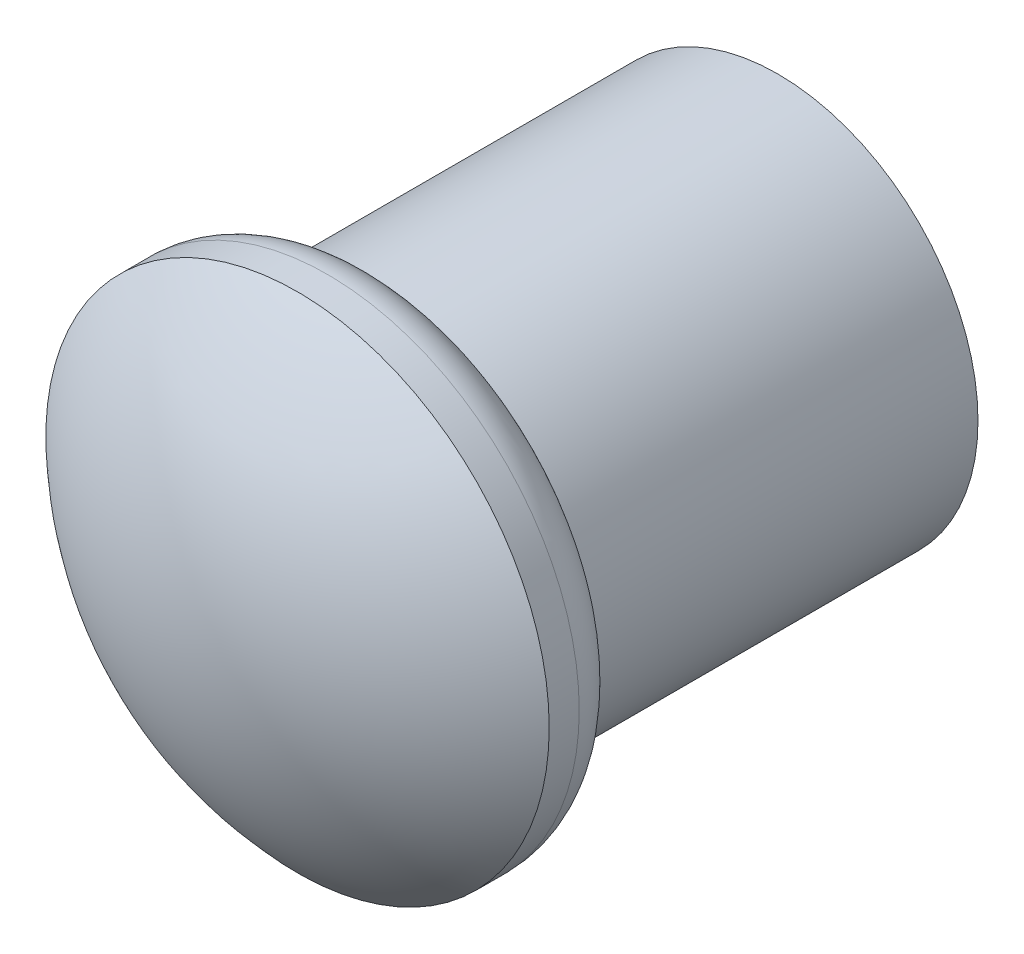
SolidWorks part; units mm, degrees
ref_plane "Front Plane" through (0, 0, 0) normal (0, 0, 1) x (1, 0, 0)
ref_plane "Top Plane" through (0, 0, 0) normal (0, 1, 0) x (1, 0, 0)
ref_plane "Right Plane" through (0, 0, 0) normal (1, 0, 0) x (0, 0, -1)
sketch "Sketch1" plane through (0, 0, 0) normal (0, 0, 1) x (1, 0, 0)
  circle A0 centre (-81.6925, 187.1174) radius 5
extrude "Boss-Extrude1" add sketch "Sketch1" along normal up to surface (10 mm away)
sketch "Sketch3" plane through (0, 0, 10) normal (0, 0, 1) x (1, 0, 0)
  circle A0 centre (-81.6925, 187.1174) radius 6.2881
extrude "Boss-Extrude2" add sketch "Sketch3" along normal blind 2
dome "Dome1" faces to dome 1 distance 2.5 reverse direction no elliptical dome no face at (-75.4044, 187.1174, 12) parameters "D1"=2.5
fillet "Fillet3" radius 1.25 1 edges at (-75.4044, 187.1174, 10)
